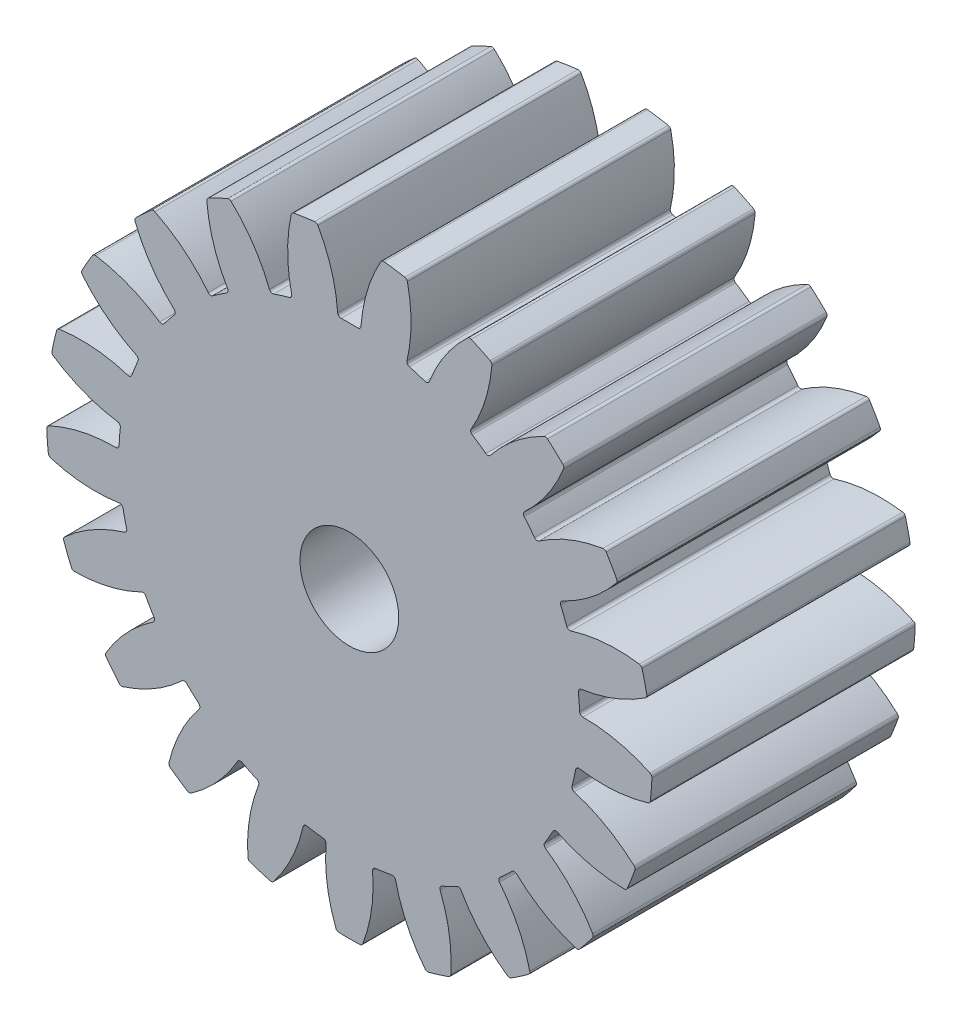
SolidWorks part; units mm, degrees
material "Нержавеющая сталь (ферритная)"
ref_plane "Спереди" through (0, 0, 0) normal (0, 0, 1) x (1, 0, 0)
ref_plane "Сверху" through (0, 0, 0) normal (0, 1, 0) x (1, 0, 0)
ref_plane "Справа" through (0, 0, 0) normal (1, 0, 0) x (0, 0, -1)
sketch "Эскиз1" plane through (0, 0, 0) normal (0, 0, 1) x (1, 0, 0)
  circle A0 centre (0, 0) radius 9.2
  circle A1 centre (0, 0) radius 1.5
  dimension "D1" = 18.4
  dimension "D2" = 3
extrude "Бобышка-Вытянуть1" add sketch "Эскиз1" along normal mid plane 8
sketch "Эскиз2" plane through (0, 0, 0) normal (0, 0, 1) x (1, 0, 0)
  line L0 (0, 0) -> (0, 9.2) construction
  line L1 (-0.3478, 6.9914) -> (0, 0) construction
  line L2 (-0.6277, 8.3765) -> (0, 6.6518) construction
  line L3 (-0.6277, 8.3765) -> (0.6277, 8.3765) construction
  line L4 (0.6277, 8.3765) -> (1.8692, 8.1894) construction
  line L5 (0, 0) -> (1.2485, 8.283) construction
  arc A0 (1.8692, 8.1894) -> (-0.6277, 8.3765) centre (0, 0) ccw construction
  arc A1 (0.3478, 6.9914) -> (-0.3478, 6.9914) centre (0, 0) ccw
  circle A2 centre (0, 0) radius 9.2 construction
  arc A3 (0.9893, 9.1467) -> (-0.9893, 9.1467) centre (0, 0) ccw
  arc A4 (0.3478, 6.9914) -> (0.9893, 9.1467) centre (5.0803, 6.7559) cw
  arc A5 (-0.3478, 6.9914) -> (-0.9893, 9.1467) centre (-5.0803, 6.7559) ccw
  dimension "D1" = 14
  dimension "D2" = 16.8
  dimension "D3" = 20
  dimension "D4" = 8.571
extrude "Вырез-Вытянуть1" cut sketch "Эскиз2" against normal through all both and the other way through all
fillet "Скругление1" radius 0.1 4 edges at (0.9893, 9.1467, 0) (0.3478, 6.9914, 0) (-0.3478, 6.9914, 0) (-0.9893, 9.1467, 0)
pattern_circular "Круговой массив1" count 21 over 360 about axis through (0, 0, 4) along (0, 0, -1) of "Вырез-Вытянуть1", "Скругление1"
equation "\"Число зубьев\" = 21"
equation "\"Модуль\"= 0.8мм"
equation "\"D1@Эскиз1\"=\"Число зубьев\"*\"Модуль\"+2*\"Модуль\""
equation "\"D2@Эскиз2\"=\"Число зубьев\"*\"Модуль\""
equation "\"D4@Эскиз2\"= 180 / \"Число зубьев\""
equation "\"D1@Круговой массив1\"=\"Число зубьев\""
